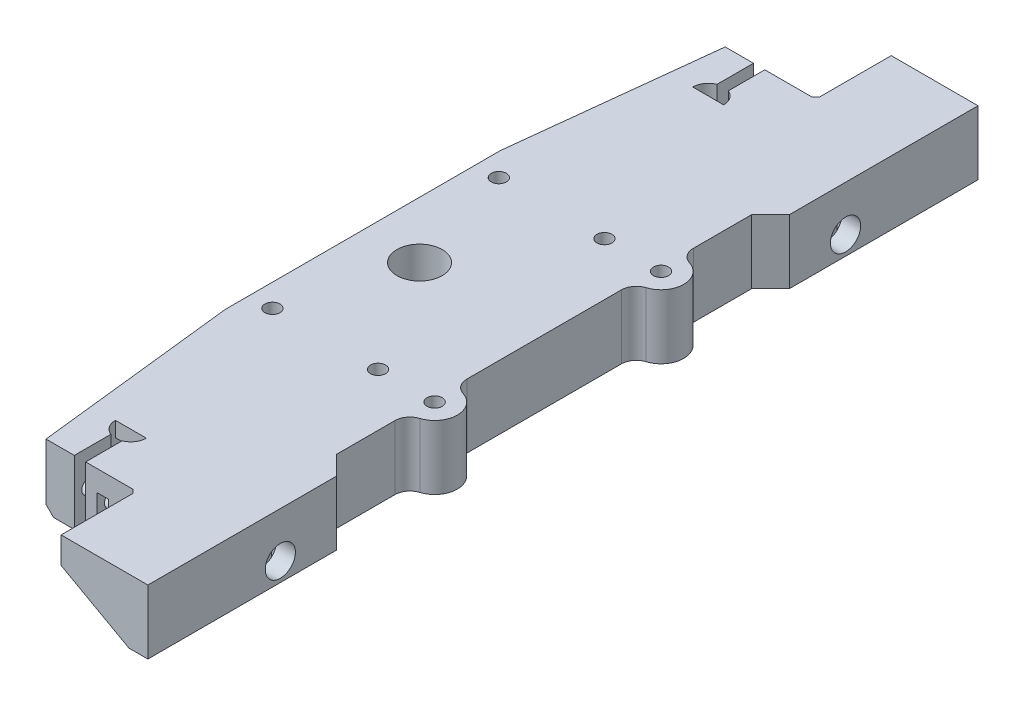
SolidWorks part; units mm, degrees
material "ABS"
ref_plane "Płaszczyzna przednia" through (0, 0, 0) normal (0, 0, 1) x (1, 0, 0)
ref_plane "Płaszczyzna górna" through (0, 0, 0) normal (0, 1, 0) x (1, 0, 0)
ref_plane "Płaszczyzna prawa" through (0, 0, 0) normal (1, 0, 0) x (0, 0, -1)
sketch "Szkic1" plane through (0, 0, 0) normal (0, 1, 0) x (1, 0, 0)
  line L0 (-20.5, 36.5) -> (-14.5, 90)
  line L1 (27.5, -90) -> (-14.5, -90)
  line L2 (27.5, -90) -> (27.5, 90)
  line L3 (27.5, 90) -> (-14.5, 90)
  line L4 (-20.5, -36.5) -> (-20.5, 36.5)
  line L5 (27.5, 0) -> (-46.9742, 0) construction
  line L6 (-7, -80.3158) -> (-7, -90)
  line L7 (-20.5, -36.5) -> (-14.5, -90)
  line L8 (-4, -80.3158) -> (-4, -90)
  line L9 (-7, 80.3158) -> (-7, 90)
  line L10 (-4, 80.3158) -> (-4, 90)
  circle A0 centre (-14.5, 30) radius 2
  circle A1 centre (13.5, 30) radius 2
  circle A4 centre (13.5, -30) radius 2
  circle A5 centre (-14.5, -30) radius 2
  circle A6 centre (-5.5, -76.5) radius 4.1
  circle A7 centre (-5.5, 0) radius 6
  circle A8 centre (-5.5, 76.5) radius 4.1
  point P0 (0, 0)
  dimension "D7" = 6
  dimension "D10" = 4
  dimension "D11" = 30
  dimension "D12" = 15
  dimension "D13" = 12
  dimension "D16" = 8.2
  dimension "D1" = 48
  dimension "D2" = 180
  dimension "D3" = 27.5
  dimension "D4" = 90
  dimension "D5" = 42
  dimension "D6" = 73
  dimension "D8" = 28
  dimension "D14" = 13.5
  dimension "D15" = 15
  dimension "D17" = 3
  dimension "D19" = 13.5
  dimension "D20" = 3
extrude "Dodanie-wyciągnięcie1" add sketch "Szkic1" along normal blind 15 contours L2 L5 A7 L4 L7 L1 L6 A6 L8 A5 A4 | L5 L2 L3 L10 A8 L9 L0 L4 A7 A0 A1 region at (4.7191, 0, -43.9009) region at (4.7191, 0, 43.9009)
sketch "Szkic3" plane through (0, 15, 0) normal (0, 1, 0) x (1, 0, 0)
  line L0 (-9.6, 76.5) -> (-1.4, 76.5)
  line L1 (-9.6, -76.5) -> (-1.4, -76.5)
  arc A0 (-7, 80.3158) -> (-4, 80.3158) centre (-5.5, 76.5) ccw construction
  arc A1 (-4, -80.3158) -> (-7, -80.3158) centre (-5.5, -76.5) ccw construction
  arc A2 (-7, 80.3158) -> (-4, 80.3158) centre (-5.5, 76.5) ccw
  arc A3 (-4, -80.3158) -> (-7, -80.3158) centre (-5.5, -76.5) ccw
  arc M7 (-4, 80.3158) -> (-7, 80.3158) centre (-5.5, 76.5) cw
  arc M15 (-7, -80.3158) -> (-4, -80.3158) centre (-5.5, -76.5) cw
extrude "Dodanie-wyciągnięcie3" add sketch "Szkic3" against normal blind 2 contours L1 M15 | L0 M7 region at (-5.5, 15, -74.7599) region at (-5.5, 15, 74.7599)
sketch "Szkic4" plane through (0, 15, 0) normal (0, 1, 0) x (1, 0, 0)
  circle A0 centre (28.5, -30) radius 2
  circle A1 centre (28.5, 30) radius 2
  circle A2 centre (13.5, 30) radius 2 construction
  circle A3 centre (13.5, -30) radius 2 construction
  circle A4 centre (13.5, 30) radius 2
  circle A5 centre (13.5, -30) radius 2
  circle A6 centre (28.5, -30) radius 6
  circle A7 centre (28.5, 30) radius 6
  line M4 (27.5, -90) -> (27.5, 90)
  dimension "D1" = 4
  dimension "D2" = 4
  dimension "D4" = 12
  dimension "D5" = 12
  dimension "D3" = 15
extrude "Dodanie-wyciągnięcie4" add sketch "Szkic4" against normal blind 15 contours A6 A0 M4 | A7 A1 M4 region at (30.8051, 15, 30) region at (30.8051, 15, -30)
sketch "Szkic5" plane through (0, 15, 0) normal (0, 1, 0) x (1, 0, 0)
  line L16 (27.5, -90) -> (27.5, -35.9161)
  line L17 (27.5, -24.0839) -> (27.5, 24.0839)
  line L18 (27.5, 35.9161) -> (27.5, 90)
  line L19 (27.5, 90) -> (-4, 90)
  line L20 (-4, 90) -> (-4, 80.3158)
  line L21 (-1.4, 76.5) -> (-9.6, 76.5)
  line L22 (-7, 80.3158) -> (-7, 90)
  line L23 (-7, 90) -> (-14.5, 90)
  line L24 (-14.5, 90) -> (-20.5, 36.5)
  line L25 (-20.5, 36.5) -> (-20.5, -36.5)
  line L26 (-20.5, -36.5) -> (-14.5, -90)
  line L27 (-14.5, -90) -> (-7, -90)
  line L28 (-7, -90) -> (-7, -80.3158)
  line L29 (-9.6, -76.5) -> (-1.4, -76.5)
  line L30 (-4, -80.3158) -> (-4, -90)
  line L31 (-4, -90) -> (27.5, -90)
  line L32 (27.5, -90) -> (27.5, -35.9161)
  line L33 (27.5, -24.0839) -> (27.5, 24.0839)
  line L34 (27.5, 35.9161) -> (27.5, 90)
  line L35 (27.5, 90) -> (-4, 90)
  line L36 (-4, 90) -> (-4, 80.3158)
  line L37 (-1.4, 76.5) -> (-9.6, 76.5)
  line L38 (-7, 80.3158) -> (-7, 90)
  line L39 (-7, 90) -> (-14.5, 90)
  line L40 (-14.5, 90) -> (-20.5, 36.5)
  line L41 (-20.5, 36.5) -> (-20.5, -36.5)
  line L42 (-20.5, -36.5) -> (-14.5, -90)
  line L43 (-14.5, -90) -> (-7, -90)
  line L44 (-7, -90) -> (-7, -80.3158)
  line L45 (-9.6, -76.5) -> (-1.4, -76.5)
  line L46 (-4, -80.3158) -> (-4, -90)
  line L47 (-4, -90) -> (27.5, -90)
  arc A0 (27.5, 28.2679) -> (27.5, 31.7321) centre (28.5, 30) ccw construction
  arc A1 (27.5, 28.2679) -> (27.5, 31.7321) centre (28.5, 30) ccw
  arc A2 (27.5, -31.7321) -> (27.5, -28.2679) centre (28.5, -30) ccw construction
  arc A3 (27.5, -31.7321) -> (27.5, -28.2679) centre (28.5, -30) ccw
  circle A4 centre (28.5, 30) radius 2
  circle A5 centre (28.5, -30) radius 2
  arc A6 (27.5, -35.9161) -> (27.5, -24.0839) centre (28.5, -30) ccw
  arc A7 (27.5, 24.0839) -> (27.5, 35.9161) centre (28.5, 30) ccw
  arc A8 (-1.4, 76.5) -> (-4, 80.3158) centre (-5.5, 76.5) ccw
  arc A9 (-7, 80.3158) -> (-9.6, 76.5) centre (-5.5, 76.5) ccw
  arc A10 (-9.6, -76.5) -> (-7, -80.3158) centre (-5.5, -76.5) ccw
  arc A11 (-4, -80.3158) -> (-1.4, -76.5) centre (-5.5, -76.5) ccw
  arc A12 (27.5, -35.9161) -> (27.5, -24.0839) centre (28.5, -30) ccw
  arc A13 (27.5, 24.0839) -> (27.5, 35.9161) centre (28.5, 30) ccw
  arc A14 (-1.4, 76.5) -> (-4, 80.3158) centre (-5.5, 76.5) ccw
  arc A15 (-7, 80.3158) -> (-9.6, 76.5) centre (-5.5, 76.5) ccw
  arc A16 (-9.6, -76.5) -> (-7, -80.3158) centre (-5.5, -76.5) ccw
  arc A17 (-4, -80.3158) -> (-1.4, -76.5) centre (-5.5, -76.5) ccw
  arc M23 (27.5, 31.7321) -> (27.5, 28.2679) centre (28.5, 30) cw
  line M24 (27.5, 28.2679) -> (27.5, 31.7321)
  arc M25 (27.5, -28.2679) -> (27.5, -31.7321) centre (28.5, -30) cw
  line M26 (27.5, -31.7321) -> (27.5, -28.2679)
  dimension "D2" = 4
  dimension "D3" = 4
  dimension "D1" = 0
extrude "Wytnij-wyciągnięcie1" cut sketch "Szkic5" against normal blind 15 contours M25 M26 | A5 M26 | A4 M24 | M23 M24 region at (28.8427, 15, -30) region at (27.09, 15, -30) region at (28.8427, 15, 30) region at (27.09, 15, 30)
fillet "Zaokrąglenie1" radius 4 4 edges at (27.5, 7.5, -35.9161) (27.5, 7.5, -24.0839) (27.5, 7.5, 24.0839) (27.5, 7.5, 35.9161)
chamfer "Sfazowanie1" distance 2 angle 45 3 edges at (-17.5, 0, -63.25) (-17.5, 0, 63.25) (-20.5, 0, 0)
sketch "Szkic8" plane through (-4, 0, 0) normal (-1, 0, 0) x (0, 0, 1)
  line L0 (90, 15) -> (90, 0) construction
  line L1 (80.3158, 15) -> (90, 15) construction
  circle A0 centre (86, 8) radius 2
  dimension "D1" = 4
  dimension "D2" = 4
  dimension "D3" = 7
extrude "Wytnij-wyciągnięcie3" cut sketch "Szkic8" along normal through all and the other way blind 7
sketch "Szkic9" plane through (-4, 0, 0) normal (-1, 0, 0) x (0, 0, 1)
  circle A0 centre (86, 8) radius 3.5
  dimension "D1" = 7
extrude "Wytnij-wyciągnięcie4" cut sketch "Szkic9" along normal blind 4 from offset 8
sketch "Szkic10" plane through (-4, 0, 0) normal (-1, 0, 0) x (0, 0, 1)
  line L0 (86, 11.4641) -> (90, 11.4641)
  line L1 (86, 11.4641) -> (83, 9.7321)
  line L2 (83, 9.7321) -> (83, 6.2679)
  line L3 (83, 6.2679) -> (86, 4.5359)
  line L4 (86, 4.5359) -> (89, 6.2679)
  line L5 (89, 6.2679) -> (89, 9.7321)
  line L6 (89, 9.7321) -> (86, 11.4641)
  line L7 (90, 15) -> (90, 0) construction
  line L8 (90, 11.4641) -> (90, 4.5359)
  line L9 (90, 4.5359) -> (86, 4.5359)
  circle A0 centre (86, 8) radius 3 construction
  circle M1 centre (86, 8) radius 2
  line M3 (90, 0) -> (90, 15)
  dimension "D1" = 6
extrude "Wytnij-wyciągnięcie5" cut sketch "Szkic10" against normal blind 3 from offset 3 contours L5 L6 L1 L2 L3 L4 M1 | L9 L0 L6 L5 L4 M3 region at (-4, 10.5187, 87.4542) region at (-4, 11.3841, 88) offset against normal yes
mirror "Lustro2" about plane through (0, 0, 0) normal (0, 0, 1) of "Wytnij-wyciągnięcie5", "Wytnij-wyciągnięcie4", "Wytnij-wyciągnięcie3"
sketch "Szkic12" plane through (0, 0, 0) normal (0, -1, 0) x (1, 0, 0)
  line L0 (27.5, 90) -> (-4, 90) construction
  line L1 (27.5, 80) -> (17.3, 80)
  line L2 (27.5, 80) -> (27.5, 69.8)
  line L3 (27.5, 69.8) -> (17.3, 69.8)
  line L4 (17.3, 80) -> (17.3, 69.8)
  line L5 (27.5, 80) -> (17.3, 69.8) construction
  line L6 (27.5, 69.8) -> (17.3, 80) construction
  line L7 (27.5, 90) -> (27.5, 39.5394) construction
  line L8 (27.5, -39.5394) -> (27.5, -90) construction
  line L9 (18.5, 78.8) -> (26.3, 78.8)
  line L10 (18.5, 78.8) -> (18.5, 71)
  line L11 (18.5, 71) -> (26.3, 71)
  line L12 (26.3, 78.8) -> (26.3, 71)
  line L13 (18.5, 78.8) -> (26.3, 71) construction
  line L14 (18.5, 71) -> (26.3, 78.8) construction
  line L15 (27.5, -69.8) -> (17.3, -69.8)
  line L16 (27.5, -69.8) -> (27.5, -80)
  line L17 (27.5, -80) -> (17.3, -80)
  line L18 (17.3, -69.8) -> (17.3, -80)
  line L19 (27.5, -69.8) -> (17.3, -80) construction
  line L20 (27.5, -80) -> (17.3, -69.8) construction
  line L21 (27.5, -90) -> (-4, -90) construction
  line L23 (18.5, -71) -> (26.3, -71)
  line L24 (18.5, -71) -> (18.5, -78.8)
  line L25 (18.5, -78.8) -> (26.3, -78.8)
  line L26 (26.3, -71) -> (26.3, -78.8)
  line L27 (18.5, -71) -> (26.3, -78.8) construction
  line L28 (18.5, -78.8) -> (26.3, -71) construction
  point P0 (22.4, 74.9)
  point P5 (22.4, -74.9)
  point P11 (22.4, 74.9)
  point P23 (22.4, -74.9)
  line M14 (27.5, -90) -> (27.5, -39.5394)
  line M22 (27.5, 39.5394) -> (27.5, 90)
  dimension "D1" = 10.2
  dimension "D2" = 20.2
  dimension "D3" = 7.8
  dimension "D4" = 10.2
  dimension "D5" = 20.2
  dimension "D6" = 7.8
extrude "Wytnij-wyciągnięcie7" cut sketch "Szkic12" against normal blind 10 contours L1 L4 L3 L9 L12 L11 L10 M22 | L15 L18 L17 L23 L26 L25 L24 M14 region at (27.3558, 0, 74.9) region at (27.3558, 0, -74.9)
sketch "Szkic13" plane through (26.3, 0, 0) normal (1, 0, 0) x (0, 0, -1)
  line L0 (78.8, 10) -> (78.8, 0) construction
  line L2 (80, 10) -> (69.8, 10) construction
  line L3 (-71, 10) -> (-71, 0) construction
  circle A0 centre (74.9, 5) radius 2
  circle A1 centre (-74.9, 5) radius 2
  dimension "D1" = 3.9
  dimension "D3" = 4
  dimension "D4" = 3.9
  dimension "D2" = 5
extrude "Wytnij-wyciągnięcie8" cut sketch "Szkic13" against normal blind 8
sketch "Szkic14" plane through (0, 0, -90) normal (0, 0, -1) x (-1, 0, 0)
  line L0 (-27.5, 0) -> (-27.5, 15)
  line L1 (-27.5, 0) -> (4, 0) construction
  line L2 (-27.5, 15) -> (4, 15) construction
  line L3 (-27.5, 15) -> (-0.4393, 15)
  line L4 (-0.4393, 15) -> (-27.5, 0)
  line L5 (-27.5, 15) -> (-27.5, 0) construction
  line L6 (-9.5, 9.9776) -> (-9.5, 15)
  line M6 (-27.5, 15) -> (-27.5, 0)
  dimension "D1" = 61
  dimension "D2" = 18
extrude "Dodanie-wyciągnięcie5" add sketch "Szkic14" along normal blind 20 contours L4 L6 L3 M6 region at (19.995, 9.5801, -90)
sketch "Szkic15" plane through (6.4636, 11.6607, 0) normal (-0.4848, -0.8746, 0) x (0.8746, -0.4848, 0)
  line L0 (24.052, -90) -> (-3.4985, -90) construction
  line L1 (3.4717, -110) -> (3.4717, -90) construction
  circle A0 centre (13.3717, -100) radius 5.1
  dimension "D1" = 10
  dimension "D3" = 10.2
  dimension "D2" = 9.9
extrude "Wytnij-wyciągnięcie9" cut sketch "Szkic15" against normal blind 7
mirror "Lustro4" about plane through (0, 0, 0) normal (0, 0, 1) of "Dodanie-wyciągnięcie5", "Wytnij-wyciągnięcie9"
chamfer "Sfazowanie2" distance 1 angle 45 4 edges at (9.5, 12.4888, -90) (18.5, 4.9888, -90) (9.5, 12.4888, 90) (18.5, 4.9888, 90)
sketch "Szkic17" plane through (0, 15, 0) normal (0, 1, 0) x (1, 0, 0)
  line L22 (27.5, -110) -> (27.5, -39.5394)
  line L23 (27.5, -20.4606) -> (27.5, 20.4606)
  line L24 (27.5, 39.5394) -> (27.5, 110)
  line L25 (27.5, 110) -> (9.5, 110)
  line L26 (9.5, 110) -> (9.5, 91)
  line L27 (9.5, 91) -> (8.5, 90)
  line L28 (8.5, 90) -> (-4, 90)
  line L29 (-4, 90) -> (-4, 80.3158)
  line L30 (-1.4, 76.5) -> (-9.6, 76.5)
  line L31 (-7, 80.3158) -> (-7, 90)
  line L32 (-7, 90) -> (-14.5, 90)
  line L33 (-14.5, 90) -> (-20.5, 36.5)
  line L34 (-20.5, 36.5) -> (-20.5, -36.5)
  line L35 (-20.5, -36.5) -> (-14.5, -90)
  line L36 (-14.5, -90) -> (-7, -90)
  line L37 (-7, -90) -> (-7, -80.3158)
  line L38 (-9.6, -76.5) -> (-1.4, -76.5)
  line L39 (-4, -80.3158) -> (-4, -90)
  line L40 (-4, -90) -> (8.5, -90)
  line L41 (8.5, -90) -> (9.5, -91)
  line L42 (9.5, -91) -> (9.5, -110)
  line L43 (9.5, -110) -> (27.5, -110)
  line L44 (27.5, -110) -> (27.5, -39.5394)
  line L45 (27.5, -20.4606) -> (27.5, 20.4606)
  line L46 (27.5, 39.5394) -> (27.5, 110)
  line L47 (27.5, 110) -> (9.5, 110)
  line L48 (9.5, 110) -> (9.5, 91)
  line L49 (9.5, 91) -> (8.5, 90)
  line L50 (8.5, 90) -> (-4, 90)
  line L51 (-4, 90) -> (-4, 80.3158)
  line L52 (-1.4, 76.5) -> (-9.6, 76.5)
  line L53 (-7, 80.3158) -> (-7, 90)
  line L54 (-7, 90) -> (-14.5, 90)
  line L55 (-14.5, 90) -> (-20.5, 36.5)
  line L56 (-20.5, 36.5) -> (-20.5, -36.5)
  line L57 (-20.5, -36.5) -> (-14.5, -90)
  line L58 (-14.5, -90) -> (-7, -90)
  line L59 (-7, -90) -> (-7, -80.3158)
  line L60 (-9.6, -76.5) -> (-1.4, -76.5)
  line L61 (-4, -80.3158) -> (-4, -90)
  line L62 (-4, -90) -> (8.5, -90)
  line L63 (8.5, -90) -> (9.5, -91)
  line L64 (9.5, -91) -> (9.5, -110)
  line L65 (9.5, -110) -> (27.5, -110)
  circle A0 centre (28.5, 30) radius 2 construction
  circle A1 centre (-14.5, 30) radius 2 construction
  circle A2 centre (13.5, 30) radius 2 construction
  circle A3 centre (-5.5, 0) radius 6 construction
  circle A4 centre (28.5, -30) radius 2 construction
  circle A5 centre (13.5, -30) radius 2 construction
  circle A6 centre (-14.5, -30) radius 2 construction
  circle A7 centre (28.5, 30) radius 2
  circle A8 centre (-14.5, 30) radius 2
  circle A9 centre (13.5, 30) radius 2
  arc A10 (30.3, -35.7236) -> (27.5, -39.5394) centre (31.5, -39.5394) ccw
  arc A11 (30.3, -35.7236) -> (30.3, -24.2764) centre (28.5, -30) ccw
  arc A12 (27.5, -20.4606) -> (30.3, -24.2764) centre (31.5, -20.4606) ccw
  arc A13 (30.3, 24.2764) -> (27.5, 20.4606) centre (31.5, 20.4606) ccw
  arc A14 (30.3, 24.2764) -> (30.3, 35.7236) centre (28.5, 30) ccw
  arc A15 (27.5, 39.5394) -> (30.3, 35.7236) centre (31.5, 39.5394) ccw
  arc A16 (-1.4, 76.5) -> (-4, 80.3158) centre (-5.5, 76.5) ccw
  arc A17 (-7, 80.3158) -> (-9.6, 76.5) centre (-5.5, 76.5) ccw
  arc A18 (-9.6, -76.5) -> (-7, -80.3158) centre (-5.5, -76.5) ccw
  arc A19 (-4, -80.3158) -> (-1.4, -76.5) centre (-5.5, -76.5) ccw
  arc A20 (30.3, -35.7236) -> (27.5, -39.5394) centre (31.5, -39.5394) ccw
  arc A21 (30.3, -35.7236) -> (30.3, -24.2764) centre (28.5, -30) ccw
  arc A22 (27.5, -20.4606) -> (30.3, -24.2764) centre (31.5, -20.4606) ccw
  arc A23 (30.3, 24.2764) -> (27.5, 20.4606) centre (31.5, 20.4606) ccw
  arc A24 (30.3, 24.2764) -> (30.3, 35.7236) centre (28.5, 30) ccw
  arc A25 (27.5, 39.5394) -> (30.3, 35.7236) centre (31.5, 39.5394) ccw
  arc A26 (-1.4, 76.5) -> (-4, 80.3158) centre (-5.5, 76.5) ccw
  arc A27 (-7, 80.3158) -> (-9.6, 76.5) centre (-5.5, 76.5) ccw
  arc A28 (-9.6, -76.5) -> (-7, -80.3158) centre (-5.5, -76.5) ccw
  arc A29 (-4, -80.3158) -> (-1.4, -76.5) centre (-5.5, -76.5) ccw
  circle A30 centre (-5.5, 0) radius 6
  circle A31 centre (28.5, -30) radius 2
  circle A32 centre (13.5, -30) radius 2
  circle A33 centre (-14.5, -30) radius 2
  dimension "D1" = 0
extrude "Dodanie-wyciągnięcie6" add sketch "Szkic17" along normal blind 2
sketch "Szkic18" plane through (27.5, 0, 0) normal (1, 0, 0) x (0, 0, -1)
  line L1 (110, 17) -> (60, 17)
  line L2 (110, 17) -> (110, 0)
  line L3 (110, 0) -> (60, 0)
  line L4 (60, 17) -> (60, 0)
  line L5 (39.5394, 0) -> (69.8, 0) construction
  line L7 (-110, 17) -> (-60, 17)
  line L8 (-110, 17) -> (-110, 0)
  line L9 (-110, 0) -> (-60, 0)
  line L10 (-60, 17) -> (-60, 0)
  line L11 (-69.8, 0) -> (-39.5394, 0) construction
  circle A0 centre (-74.9, 5) radius 4
  circle A1 centre (74.9, 5) radius 4
  dimension "D5" = 8
  dimension "D1" = 17
  dimension "D2" = 50
  dimension "D3" = 17
  dimension "D4" = 50
extrude "Dodanie-wyciągnięcie7" add sketch "Szkic18" along normal blind 5
chamfer "Sfazowanie3" distance 5 angle 45 2 edges at (27.5, 8.5, 60) (27.5, 8.5, -60)
